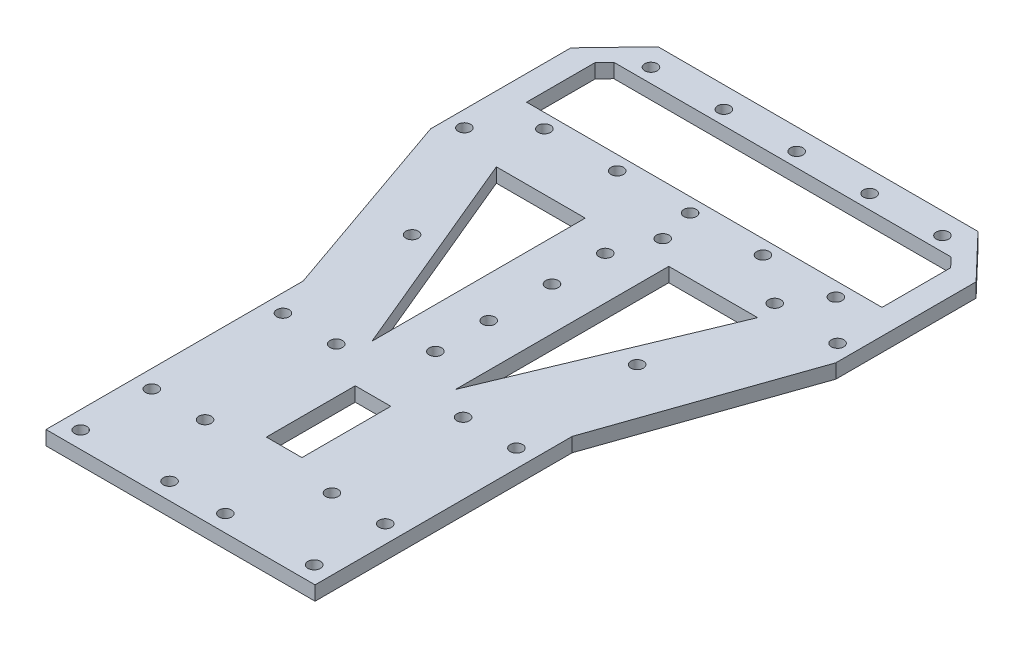
SolidWorks part; units mm, degrees
note: The reader was unsure of these and kept them because the rebuilt part matched: shared geometry of "Sketch3<3>", "Sketch6<3>".
ref_plane "Front Plane" through (0, 0, 0) normal (0, 0, 1) x (1, 0, 0)
ref_plane "Top Plane" through (0, 0, 0) normal (0, 1, 0) x (1, 0, 0)
ref_plane "Right Plane" through (0, 0, 0) normal (1, 0, 0) x (0, 0, -1)
sketch "Sketch1" plane through (0, 0, 0) normal (0, 1, 0) x (1, 0, 0)
  line L1 (-37.85, 21.35) -> (37.85, 21.35)
  line L2 (-37.85, 21.35) -> (-37.85, -21.35)
  line L3 (-37.85, -21.35) -> (37.85, -21.35)
  line L4 (37.85, 21.35) -> (37.85, -21.35)
  line L5 (-37.85, 21.35) -> (37.85, -21.35) construction
  line L6 (-37.85, -21.35) -> (37.85, 21.35) construction
  circle A0 centre (2.4, 17.25) radius 1.75
  circle A1 centre (-33.8, -17.05) radius 1.75
  circle A2 centre (29.5, -17.05) radius 1.75
  circle A3 centre (33.9, 17.25) radius 1.75
  point P0 (0, 0)
  dimension "D9" = 3.5
  dimension "D1" = 75.7
  dimension "D2" = 42.7
  dimension "D3" = 4.1
  dimension "D4" = 4.3
  dimension "D5" = 4.05
  dimension "D6" = 8.35
  dimension "D7" = 3.95
  dimension "D8" = 40.25
extrude "Boss-Extrude1" add sketch "Sketch1" along normal blind 4
sketch "Sketch3" plane through (0, 4, 0) normal (0, 1, 0) x (1, 0, 0)
  line L0 (0, 0) -> (-31.5, 0) construction
  line L1 (-2.2, 0) -> (2.2, 0) construction
  line L2 (-31.5, 0) -> (-31.5, 14.5) construction
  line L3 (-31.5, 14.5) -> (27.3, 14.5) construction
  line L4 (27.3, 14.5) -> (27.3, -51.1) construction
  line L5 (27.3, -51.1) -> (-31.5, -51.1) construction
  line L6 (-31.5, -51.1) -> (-31.5, 0) construction
  line L7 (-2.1, 80.1) -> (-2.1, -51.1)
  line L9 (-31.5, -18.3) -> (27.3, -18.3) construction
  line L10 (-37.85, -21.35) -> (-37.85, -51.1)
  line L11 (37.85, -21.35) -> (37.85, -51.1)
  line L12 (37.85, -51.1) -> (-37.85, -51.1)
  line L13 (-37.85, -21.35) -> (37.85, -21.35)
  line L14 (-2.1, 5.6) -> (-2.1, -9.4) construction
  line L16 (0, -2.2) -> (0, 2.2) construction
  circle A0 centre (-2.1, 5.6) radius 1.75
  circle A1 centre (-2.1, -9.4) radius 1.75
  circle A2 centre (-2.1, -27.2) radius 1.75
  circle A3 centre (-2.1, -42.2) radius 1.75
  point P12 (-2.1, 14.5)
  line M18 (-37.85, -21.35) -> (37.85, -21.35)
  dimension "D10" = 3.5
  dimension "D1" = 58.8
  dimension "D2" = 29.4
  dimension "D3" = 65.6
  dimension "D4" = 14.5
  dimension "D5" = 32.8
  dimension "D6" = 15
  dimension "D7" = 15
  dimension "D8" = 8.9
  dimension "D9" = 8.9
  dimension "D11" = 31.5
extrude "Boss-Extrude2" add sketch "Sketch3" against normal blind 4 contours L12 L11 L10 A3 A2 M18 | A3 L7 A2 L10 L12 M18
extrude "Cut-Extrude1" cut sketch "Sketch3<3>" against normal blind 4 contours A0 | A1
sketch "Sketch3<3>" plane through (0, 4, 0) normal (0, 1, 0) x (1, 0, 0) same geometry as "Sketch3"
sketch "Sketch4" plane through (0, 0, 0) normal (0, 1, 0) x (1, 0, 0)
  line L0 (-37.85, -51.1) -> (-37.85, -94.5) construction
  line L1 (-37.85, -94.5) -> (37.85, -94.5) construction
  line L2 (37.85, 21.35) -> (44, 21.35) construction
  line L3 (44, 21.35) -> (44, 29.35) construction
  line L4 (-37.85, 21.35) -> (-44, 21.35) construction
  line L6 (37.85, -51.1) -> (37.85, -94.5) construction
  line L7 (-44, 21.35) -> (-44, 29.35) construction
  line L8 (-44, 29.35) -> (44, 29.35) construction
  line L10 (-37.85, -51.1) -> (-37.85, -94.5)
  line L11 (-37.85, -94.5) -> (37.85, -94.5)
  line L12 (37.85, -94.5) -> (37.85, -51.1)
  line L13 (37.85, -51.1) -> (-37.85, -51.1)
  line L14 (-37.85, 21.35) -> (-44, 21.35)
  line L15 (-44, 21.35) -> (-44, 29.35)
  line L16 (-44, 29.35) -> (44, 29.35)
  line L17 (44, 29.35) -> (44, 21.35)
  line L18 (44, 21.35) -> (37.85, 21.35)
  line L19 (37.85, 21.35) -> (-37.85, 21.35)
  line L20 (0, -2.2) -> (0, 2.2) construction
  circle A0 centre (-32.85, -54.35) radius 1.75
  circle A1 centre (-17.85, -54.35) radius 1.75
  circle A2 centre (-17.85, -91.25) radius 1.75
  circle A3 centre (-32.85, -91.25) radius 1.75
  circle A4 centre (32.85, -91.25) radius 1.75
  circle A5 centre (17.85, -91.25) radius 1.75
  circle A6 centre (17.85, -54.35) radius 1.75
  circle A7 centre (32.85, -54.35) radius 1.75
  dimension "D5" = 3.5
  dimension "D1" = 88
  dimension "D2" = 8
  dimension "D3" = 43.4
  dimension "D4" = 6.15
  dimension "D6" = 15
  dimension "D7" = 5
  dimension "D8" = 3.25
  dimension "D9" = 3.25
extrude "Boss-Extrude3" add sketch "Sketch4" along normal blind 4
sketch "Sketch6" plane through (0, 4, 0) normal (0, 1, 0) x (1, 0, 0)
  line L0 (-44, 27.35) -> (44, 27.35) construction
  line L1 (-44, 29.35) -> (-44, 21.35) construction
  line L2 (44, 21.35) -> (44, 29.35) construction
  line L4 (-57, 29.35) -> (-57, 21.35)
  line L5 (-57, 21.35) -> (-44, 21.35)
  line L7 (57, 29.35) -> (57, 21.35)
  line L8 (57, 21.35) -> (44, 21.35)
  line L9 (44, 21.35) -> (44, 26.2514)
  line L10 (44, 29.35) -> (44, 26.2514)
  line L11 (-44, 21.35) -> (-44, 26.2514)
  line L12 (-44, 29.35) -> (-44, 26.2514)
  line L13 (44, 29.35) -> (-44, 29.35) construction
  line L14 (-57, 29.35) -> (-57, 31.35)
  line L15 (-57, 31.35) -> (57, 31.35)
  line L16 (57, 31.35) -> (57, 29.35)
  line L17 (44, 29.35) -> (-44, 29.35)
  line L18 (0, -2.2) -> (0, 2.2) construction
  circle A0 centre (0, 27.35) radius 1.75
  circle A1 centre (20.5, 27.35) radius 1.75
  circle A2 centre (41, 27.35) radius 1.75
  circle A3 centre (-20.5, 27.35) radius 1.75
  circle A4 centre (-41, 27.35) radius 1.75
  point P29 (0, 0)
  point P31 (0, 0)
  dimension "D5" = 3.5
  dimension "D1" = 20.5
  dimension "D2" = 20.5
  dimension "D3" = 20.5
  dimension "D4" = 20.5
  dimension "D6" = 16
  dimension "D7" = 16
  dimension "D8" = 2
  dimension "D9" = 2
  dimension "D10" = 2
extrude "Boss-Extrude4" add sketch "Sketch6" against normal blind 4
extrude "Cut-Extrude2" cut sketch "Sketch6<3>" against normal through all contours A4 | A3 | A1 | A2 | A0
sketch "Sketch6<3>" plane through (0, 4, 0) normal (0, 1, 0) x (1, 0, 0) same geometry as "Sketch6"
sketch "Sketch7" plane through (0, 0, 0) normal (0, 1, 0) x (1, 0, 0)
  line L0 (-57, 21.35) -> (-57, 11.35)
  line L1 (-57, 11.35) -> (-37.85, 11.35)
  line L2 (-37.85, 21.35) -> (-37.85, -94.5) construction
  line L3 (-37.85, 11.35) -> (-37.85, 21.35)
  line L4 (-37.85, 21.35) -> (-57, 21.35)
  line L5 (57, 21.35) -> (57, 11.35)
  line L6 (57, 11.35) -> (37.85, 11.35)
  line L7 (37.85, -94.5) -> (37.85, 21.35) construction
  line L8 (37.85, 11.35) -> (37.85, 21.35)
  line L9 (37.85, 21.35) -> (57, 21.35)
  circle A0 centre (-52.5, 16.35) radius 1.75
  circle A1 centre (52.5, 16.35) radius 1.75
  dimension "D6" = 3.5
  dimension "D1" = 10
  dimension "D2" = 10
  dimension "D3" = 4.5
  dimension "D4" = 4.5
  dimension "D5" = 5
extrude "Boss-Extrude5" add sketch "Sketch7" along normal blind 4
sketch "Sketch8" plane through (0, 0, 0) normal (0, 1, 0) x (1, 0, 0)
  line L0 (-37.85, -94.5) -> (-37.85, -116)
  line L1 (-37.85, -116) -> (37.85, -116)
  line L2 (37.85, -116) -> (37.85, -94.5)
  line L3 (-37.85, -94.5) -> (37.85, -94.5)
  dimension "D1" = 21.5
extrude "Boss-Extrude6" add sketch "Sketch8" along normal blind 4
sketch "Sketch9" plane through (0, 4, 0) normal (0, 1, 0) x (1, 0, 0)
  line L0 (-37.85, -116) -> (-2.85, -116) construction
  line L1 (-37.85, -116) -> (37.85, -116) construction
  line L2 (-2.85, -116) -> (-2.85, -103.1) construction
  line L3 (-2.85, -103.1) -> (-37.85, -103.1) construction
  line L4 (-37.85, 11.35) -> (-37.85, -116) construction
  line L5 (-37.85, -103.1) -> (-37.85, -116) construction
  circle A2 centre (-7.85, -111.25) radius 1.75
  circle A3 centre (-32.85, -111.25) radius 1.75
  circle A4 centre (-32.85, -91.25) radius 1.75 construction
  dimension "D7" = 3.5
  dimension "D1" = 20
  dimension "D2" = 35
  dimension "D3" = 5
  dimension "D4" = 5
extrude "Cut-Extrude3" cut sketch "Sketch9" against normal through all
mirror "Mirror1" about plane through (0, 0, 0) normal (1, 0, 0) of "Cut-Extrude3"
sketch "Sketch10" plane through (0, 4, 0) normal (0, 1, 0) x (1, 0, 0)
  line L0 (-57, 11.35) -> (-37.85, -43.65)
  line L1 (-37.85, 11.35) -> (-37.85, -116) construction
  line L2 (57, 11.35) -> (37.85, -43.65)
  line L3 (37.85, -116) -> (37.85, 11.35) construction
  line L4 (37.85, -43.65) -> (37.85, 11.35)
  line L5 (37.85, 11.35) -> (57, 11.35)
  line L6 (-57, 11.35) -> (-37.85, 11.35)
  line L7 (-37.85, 11.35) -> (-37.85, -43.65)
  dimension "D1" = 55
  dimension "D2" = 55
extrude "Boss-Extrude7" add sketch "Sketch10" against normal blind 4
sketch "Sketch11" plane through (0, 4, 0) normal (0, 1, 0) x (1, 0, 0)
  line L0 (-38.5, 11.35) -> (-13.5, 11.35)
  line L1 (-13.5, 11.35) -> (-13.5, -48.65)
  line L2 (-13.5, -48.65) -> (-38.5, 11.35)
  line L3 (10, 11.35) -> (35, 11.35)
  line L4 (35, 11.35) -> (10, -48.65)
  line L5 (10, -48.65) -> (10, 11.35)
  line L6 (-13.5, 11.35) -> (0, 11.35) construction
  line L7 (0, -2.2) -> (0, 2.2) construction
  line L8 (0, 11.35) -> (10, 11.35) construction
  dimension "D1" = 60
  dimension "D2" = 10
  dimension "D3" = 25
  dimension "D4" = 13.5
extrude "Cut-Extrude4" cut sketch "Sketch11" against normal blind 4
sketch "Sketch12" plane through (0, 4, 0) normal (0, 1, 0) x (1, 0, 0)
  line L0 (0, -2.2) -> (0, 2.2) construction
  line L1 (-5, -61.85) -> (5, -61.85)
  line L2 (-5, -61.85) -> (-5, -86.85)
  line L3 (-5, -86.85) -> (5, -86.85)
  line L4 (5, -61.85) -> (5, -86.85)
  line L5 (-5, -61.85) -> (5, -86.85) construction
  line L6 (-5, -86.85) -> (5, -61.85) construction
  circle A0 centre (17.85, -54.35) radius 1.75 construction
  point P0 (0, -74.35)
  dimension "D1" = 10
  dimension "D2" = 20
  dimension "D3" = 25
extrude "Cut-Extrude5" cut sketch "Sketch12" against normal blind 10
sketch "Sketch13" plane through (0, 0, 0) normal (0, 1, 0) x (1, 0, 0)
  line L0 (-57, 31.35) -> (-57, 50.8107)
  line L1 (-57, 50.8107) -> (-45, 63.35)
  line L2 (-45, 63.35) -> (45, 63.35)
  line L3 (45, 63.35) -> (57, 50.8107)
  line L4 (57, 50.8107) -> (57, 31.35)
  line L6 (-50, 31.35) -> (-50, 50.6577)
  line L7 (-50, 50.6577) -> (-47.4235, 53.35)
  line L8 (-47.4235, 53.35) -> (47.4235, 53.35)
  line L9 (47.4235, 53.35) -> (50, 50.6577)
  line L10 (50, 50.6577) -> (50, 31.35)
  line L22 (-41, 27.35) -> (-41, 63.35) construction
  line L23 (-20.5, 27.35) -> (-20.5, 63.35) construction
  line L24 (20.5, 27.35) -> (20.5, 63.35) construction
  line L25 (41, 27.35) -> (41, 63.35) construction
  line L26 (-41, 57.35) -> (41, 57.35) construction
  line L27 (-57, 31.35) -> (57, 31.35) construction
  line L28 (-57, 31.35) -> (-50, 31.35)
  line L29 (50, 31.35) -> (57, 31.35)
  circle A0 centre (-41, 27.35) radius 1.75 construction
  circle A1 centre (-41, 57.35) radius 1.75
  circle A2 centre (-20.5, 57.35) radius 1.75
  circle A3 centre (0, 57.35) radius 1.75
  circle A4 centre (20.5, 57.35) radius 1.75
  circle A5 centre (41, 57.35) radius 1.75
  point P7 (50, 50.8107)
  dimension "D2" = 9
  dimension "D6" = 3.5
  dimension "D1" = 22
  dimension "D3" = 32
  dimension "D4" = 7
  dimension "D5" = 30
  dimension "D7" = 90
extrude "Boss-Extrude8" add sketch "Sketch13" along normal blind 4
